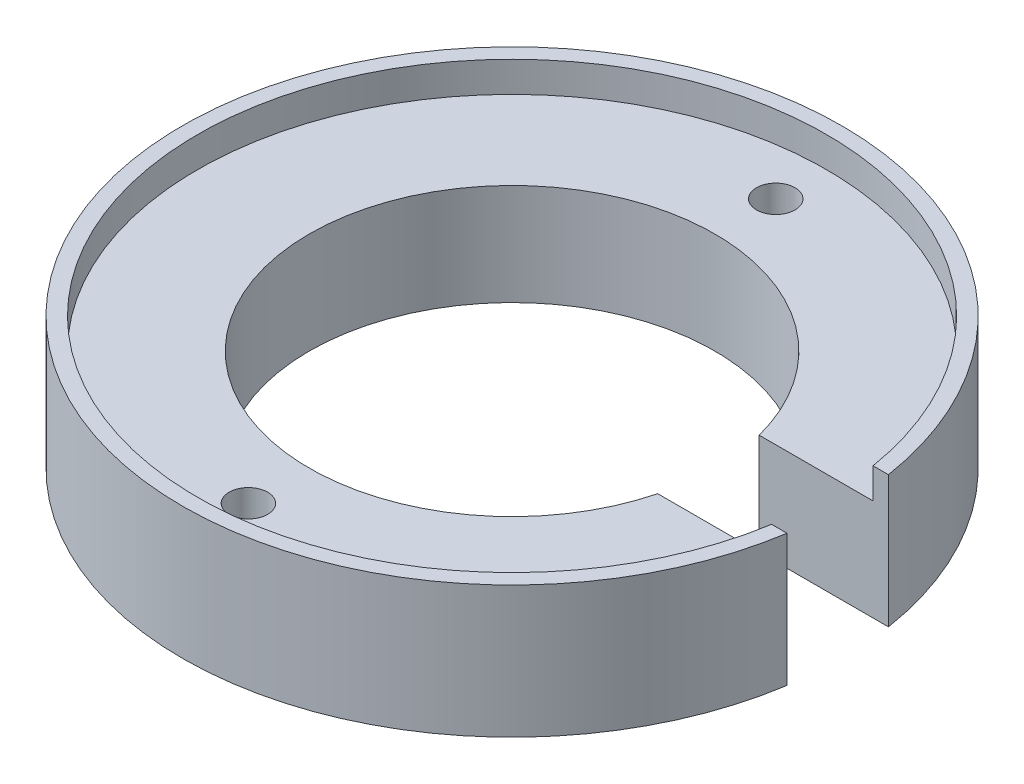
SolidWorks part; units mm, degrees
ref_plane "Front Plane" through (0, 0, 0) normal (0, 0, 1) x (1, 0, 0)
ref_plane "Top Plane" through (0, 0, 0) normal (0, 1, 0) x (1, 0, 0)
ref_plane "Right Plane" through (0, 0, 0) normal (1, 0, 0) x (0, 0, -1)
sketch "Sketch1" plane through (0, 0, 0) normal (0, 1, 0) x (1, 0, 0)
  circle A0 centre (0, 0) radius 32.5
  dimension "D1" = 65
extrude "Boss-Extrude1" add sketch "Sketch1" along normal blind 10
sketch "Sketch2" plane through (0, 10, 0) normal (0, 1, 0) x (1, 0, 0)
  circle A0 centre (0, 0) radius 31
  circle A2 centre (0, 0) radius 32.5
  circle A3 centre (0, 0) radius 32.5
  dimension "D1" = 62
  dimension "D2" = 0
extrude "Boss-Extrude2" add sketch "Sketch2" along normal blind 3
sketch "Sketch3" plane through (0, 10, 0) normal (0, 1, 0) x (1, 0, 0)
  line L1 (0, 5) -> (39.8185, 5)
  line L2 (0, 5) -> (0, -5)
  line L3 (0, -5) -> (39.8185, -5)
  line L4 (39.8185, 5) -> (39.8185, -5)
  line L5 (0, 5) -> (39.8185, -5) construction
  line L6 (0, -5) -> (39.8185, 5) construction
  point P0 (19.9092, 0)
  dimension "D1" = 10
extrude "Cut-Extrude1" cut sketch "Sketch3" against normal through all and the other way blind 3
fillet "Fillet1" radius 5 2 edges at (0, 5, 5) (0, 5, -5)
hole_wizard "Ø3.8 (3.8) Diameter Hole1" positions "Sketch5" profile "Sketch4" hole size "Ø3.8" standard "ISO"
sketch "Sketch5" plane through (0, 10, 0) normal (0, 1, 0) x (1, 0, 0)
  line L0 (0, -26) -> (0, 26) construction
  point P0 (0, 26)
  point P2 (0, -26)
  dimension "D1" = 52
sketch "Sketch4" plane through (0, 10, -26) normal (1, 0, 0) x (0, 0, 1)
  line L0 (0, 0) -> (0, 11.1416)
  line L1 (0, 11.1416) -> (1.9, 10)
  line L2 (1.9, 10) -> (1.9, 0)
  line L5 (1.9, 0) -> (0, 0)
  line L10 (0, 11.1416) -> (-1.9, 10) construction
  line L11 (0, -6.35) -> (0, 107.95) construction
  dimension "Hole Dia." = 3.8
  dimension "Hole Depth" = 10
  dimension "Drill Angle" = 118
sketch "Sketch6" plane through (0, 10, 0) normal (0, 1, 0) x (1, 0, 0)
  circle A0 centre (0, 0) radius 20
  dimension "D1" = 40
extrude "Cut-Extrude2" cut sketch "Sketch6" against normal blind 10
